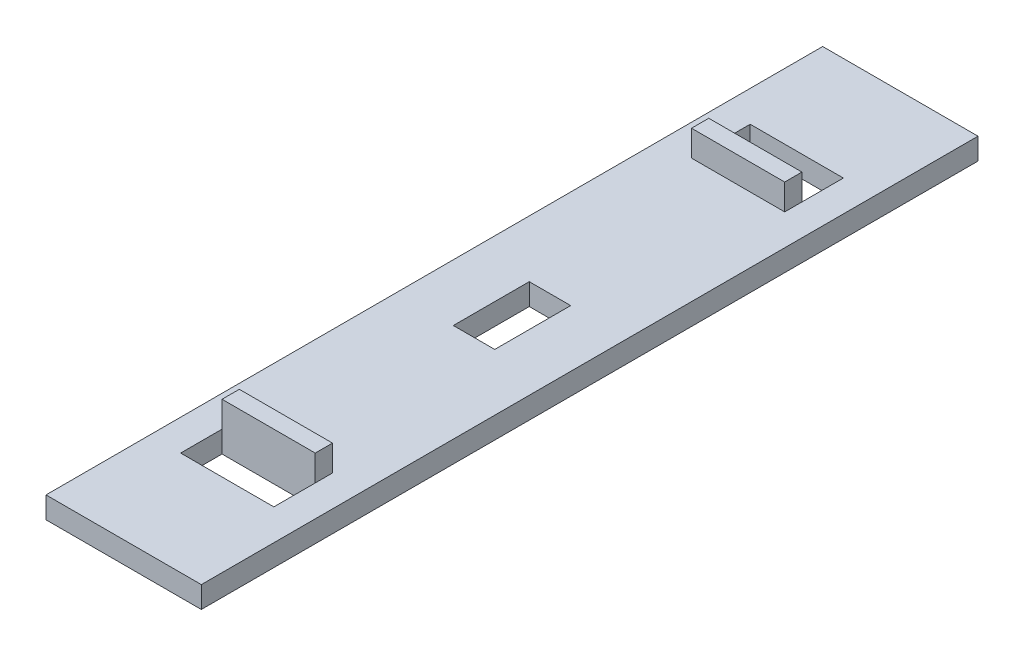
SolidWorks part; units mm, degrees
ref_plane "Plan de face" through (0, 0, 0) normal (0, 0, 1) x (1, 0, 0)
ref_plane "Plan de dessus" through (0, 0, 0) normal (0, 1, 0) x (1, 0, 0)
ref_plane "Plan de droite" through (0, 0, 0) normal (1, 0, 0) x (0, 0, -1)
sketch "Esquisse1" plane through (0, 0, 0) normal (0, 1, 0) x (1, 0, 0)
  line L0 (3.409, -1.8775) -> (3.409, 4.1225) construction
  line L1 (-1.091, 43.1225) -> (7.909, 43.1225)
  line L2 (-1.091, 43.1225) -> (-1.091, -1.8775)
  line L3 (-1.091, -1.8775) -> (7.909, -1.8775)
  line L4 (7.909, 43.1225) -> (7.909, -1.8775)
  line L5 (0.709, 4.1225) -> (6.109, 4.1225)
  line L6 (0.709, 4.1225) -> (0.709, 6.5225)
  line L7 (0.709, 6.5225) -> (6.109, 6.5225)
  line L8 (6.109, 4.1225) -> (6.109, 6.5225)
  line L9 (-1.091, 20.6225) -> (7.909, 20.6225) construction
  line L10 (0.709, 34.7225) -> (6.109, 34.7225)
  line L11 (6.109, 37.1225) -> (6.109, 34.7225)
  line L12 (0.709, 37.1225) -> (6.109, 37.1225)
  line L13 (0.709, 37.1225) -> (0.709, 34.7225)
  dimension "D1" = 45
  dimension "D2" = 9
  dimension "D3" = 6
  dimension "D4" = 5.4
  dimension "D5" = 2.4
extrude "Boss.-Extru.1" add sketch "Esquisse1" along normal blind 1.25 contours L4 L1 L2 L3 L13 L12 L11 L10 L8 L5 L6 L7 region at (3.409, 0, -20.6225)
sketch "Esquisse2" plane through (0, 0, 0) normal (0, -1, 0) x (1, 0, 0)
  line L0 (-1.091, -20.6225) -> (7.909, -20.6225) construction
  line L1 (-1.091, -43.1225) -> (-1.091, 1.8775) construction
  line L2 (7.909, -43.1225) -> (7.909, 1.8775) construction
  line L4 (4.609, -22.8225) -> (2.209, -22.8225)
  line L5 (4.609, -22.8225) -> (4.609, -18.4225)
  line L6 (4.609, -18.4225) -> (2.209, -18.4225)
  line L7 (2.209, -22.8225) -> (2.209, -18.4225)
  line L8 (4.609, -22.8225) -> (2.209, -18.4225) construction
  line L9 (4.609, -18.4225) -> (2.209, -22.8225) construction
  point P6 (3.409, -20.6225)
  point P11 (3.409, -20.6225)
  dimension "D1" = 4.4
  dimension "D2" = 2.4
extrude "Enlèv. mat.-Extru.1" cut sketch "Esquisse2" along normal through all and the other way through all contours L7 L4 L5 L6 region at (3.409, 0, -20.6225)
sketch "Esquisse3" plane through (0, 1.25, 0) normal (0, 1, 0) x (1, 0, 0)
  line L0 (0.709, 6.5225) -> (6.109, 6.5225)
  line L1 (0.709, 6.5225) -> (0.709, 7.5225)
  line L2 (6.109, 6.5225) -> (6.109, 7.5225)
  line L3 (0.709, 7.5225) -> (6.109, 7.5225)
  line L4 (-1.091, 20.6225) -> (7.909, 20.6225) construction
  line L5 (-1.091, 43.1225) -> (-1.091, -1.8775) construction
  line L6 (7.909, 43.1225) -> (7.909, -1.8775) construction
  line L7 (6.109, 34.7225) -> (6.109, 33.7225)
  line L8 (0.709, 33.7225) -> (6.109, 33.7225)
  line L9 (0.709, 34.7225) -> (0.709, 33.7225)
  line L10 (0.709, 34.7225) -> (6.109, 34.7225)
  dimension "D1" = 1
extrude "Boss.-Extru.2" add sketch "Esquisse3" along normal blind 1.5
